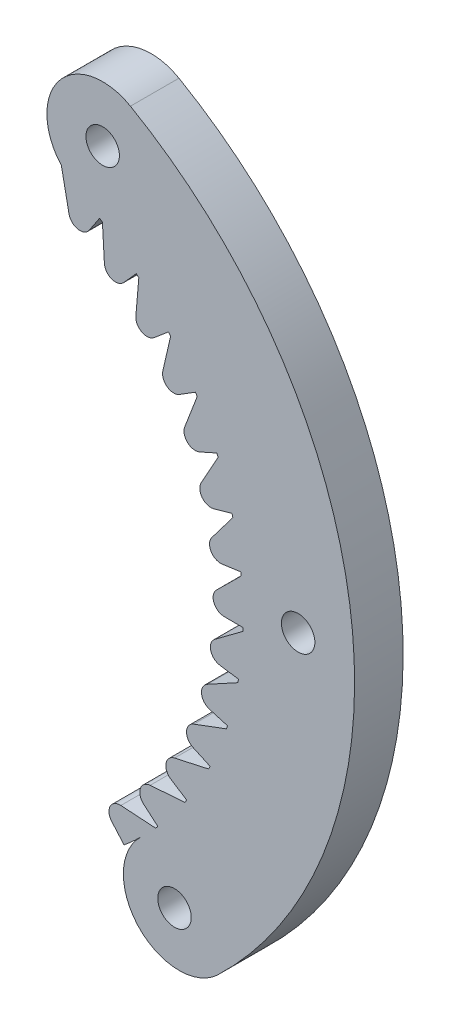
SolidWorks part; units mm, degrees
ref_plane "Plan de face" through (0, 0, 0) normal (0, 0, 1) x (1, 0, 0)
ref_plane "Plan de dessus" through (0, 0, 0) normal (0, 1, 0) x (1, 0, 0)
ref_plane "Plan de droite" through (0, 0, 0) normal (1, 0, 0) x (0, 0, -1)
sketch "Esquisse1" plane through (0, 0, 0) normal (0, 0, 1) x (1, 0, 0)
  line L0 (-13.1833, -31.6794) -> (-0.7137, -32.0392)
  arc A0 (-6.6972, -24.0098) -> (-13.1833, -31.6794) centre (12.6433, -46.9433) ccw
  arc A1 (-0.7137, -32.0392) -> (-6.1287, 33.617) centre (-26.0378, -1.0764) ccw
  arc A2 (-6.1287, 33.617) -> (-11.106, 24.9437) centre (-8.6173, 29.2803) ccw
  arc A3 (-6.6972, -24.0098) -> (-11.106, 24.9437) centre (-26.0378, -1.0764) ccw
extrude "Boss.-Extru.1" add sketch "Esquisse1" along normal blind 4.35
sketch "Esquisse2" plane through (0, 0, 0) normal (0, 0, -1) x (-1, 0, 0)
  line L0 (13.1833, -31.6794) -> (0.7137, -32.0392) construction
  line L1 (13.1833, -31.6794) -> (0.7137, -32.0392)
  arc A0 (0.7137, -32.0392) -> (6.6972, -24.0098) centre (0.5296, -25.6578) ccw
  arc A1 (13.1833, -31.6794) -> (6.6972, -24.0098) centre (-12.6433, -46.9433) ccw construction
  arc A2 (13.1833, -31.6794) -> (6.6972, -24.0098) centre (-12.6433, -46.9433) ccw
extrude "Enlèv. mat.-Extru.1" cut sketch "Esquisse2" against normal through all
fillet "Congé3" radius 5 2 edges at (-0.7137, -32.0392, 2.175) (-6.6972, -24.0098, 2.175)
sketch "Esquisse3" plane through (0, 0, 4.35) normal (0, 0, 1) x (1, 0, 0)
  circle A0 centre (-8.6173, 29.2803) radius 1.5
  circle A1 centre (8.9018, 0.2577) radius 1.5
  circle A2 centre (-2.1801, -26.6398) radius 1.5
extrude "Enlèv. mat.-Extru.2" cut sketch "Esquisse3" against normal through all
sketch "Esquisse4" plane through (0, 0, 4.35) normal (0, 0, 1) x (1, 0, 0)
  line L0 (-3.6669, -21.0649) -> (-4.9406, -19.9723) construction
  line L1 (-4.3658, -18.2162) -> (-1.2519, -17.9779) construction
  line L2 (-8.8914, 23.5408) -> (-9.8225, 22.1447) construction
  line L3 (-11.6351, 22.5036) -> (-12.247, 25.566) construction
  line L4 (-12.247, 25.566) -> (-12.3172, 25.9171) construction
  line L5 (-6.6972, -24.0098) -> (-7.8048, -22.7491) construction
  line L6 (-6.989, -21.0912) -> (-3.8725, -21.2928) construction
  line L7 (3.5531, -6.014) -> (1.8926, -5.7713) construction
  line L8 (1.4399, -3.9799) -> (3.9443, -2.1142) construction
  line L9 (2.5658, -10.1226) -> (0.9559, -9.649) construction
  line L10 (0.7593, -7.8118) -> (3.5011, -6.3165) construction
  line L11 (1.0111, -14.0518) -> (-0.5163, -13.3567) construction
  line L12 (-0.4528, -11.51) -> (2.4718, -10.4148) construction
  line L13 (-1.0803, -17.7235) -> (-2.4949, -16.8207) construction
  line L14 (-2.1726, -15.0013) -> (0.8769, -14.3278) construction
  line L15 (2.9726, 6.5654) -> (1.3588, 6.1053) construction
  line L16 (0.2107, 7.5531) -> (1.7288, 10.2822) construction
  line L17 (3.7586, 2.4136) -> (2.0961, 2.1848) construction
  line L18 (1.1628, 3.7795) -> (3.0493, 6.2683) construction
  line L19 (3.9533, -1.8075) -> (2.2752, -1.8005) construction
  line L20 (1.5753, -0.0904) -> (3.7927, 2.1086) construction
  line L21 (-2.7195, 17.7984) -> (-4.0022, 16.7165) construction
  line L22 (-5.6434, 17.5655) -> (-5.3791, 20.6773) construction
  line L23 (-0.2988, 14.3349) -> (-1.7209, 13.444) construction
  line L24 (-3.2265, 14.5152) -> (-2.5276, 17.5589) construction
  line L25 (1.6112, 10.5657) -> (0.078, 9.8833) construction
  line L26 (-1.2621, 11.1554) -> (-0.1425, 14.0708) construction
  line L27 (-5.6027, 20.8875) -> (-6.7208, 19.636) construction
  line L28 (-8.4649, 20.2461) -> (-8.6405, 23.3641) construction
  line L29 (-3.6669, -21.0649) -> (-4.9406, -19.9723)
  line L30 (-4.3658, -18.2162) -> (-1.2519, -17.9779)
  line L31 (-8.8914, 23.5408) -> (-9.8225, 22.1447)
  line L32 (-11.6351, 22.5036) -> (-12.247, 25.566)
  line L33 (-12.247, 25.566) -> (-12.3172, 25.9171)
  line L34 (-6.6972, -24.0098) -> (-7.8048, -22.7491)
  line L35 (-6.989, -21.0912) -> (-3.8725, -21.2928)
  line L36 (3.5531, -6.014) -> (1.8926, -5.7713)
  line L37 (1.4399, -3.9799) -> (3.9443, -2.1142)
  line L38 (2.5658, -10.1226) -> (0.9559, -9.649)
  line L39 (0.7593, -7.8118) -> (3.5011, -6.3165)
  line L40 (1.0111, -14.0518) -> (-0.5163, -13.3567)
  line L41 (-0.4528, -11.51) -> (2.4718, -10.4148)
  line L42 (-1.0803, -17.7235) -> (-2.4949, -16.8207)
  line L43 (-2.1726, -15.0013) -> (0.8769, -14.3278)
  line L44 (2.9726, 6.5654) -> (1.3588, 6.1053)
  line L45 (0.2107, 7.5531) -> (1.7288, 10.2822)
  line L46 (3.7586, 2.4136) -> (2.0961, 2.1848)
  line L47 (1.1628, 3.7795) -> (3.0493, 6.2683)
  line L48 (3.9533, -1.8075) -> (2.2752, -1.8005)
  line L49 (1.5753, -0.0904) -> (3.7927, 2.1086)
  line L50 (-2.7195, 17.7984) -> (-4.0022, 16.7165)
  line L51 (-5.6434, 17.5655) -> (-5.3791, 20.6773)
  line L52 (-0.2988, 14.3349) -> (-1.7209, 13.444)
  line L53 (-3.2265, 14.5152) -> (-2.5276, 17.5589)
  line L54 (1.6112, 10.5657) -> (0.078, 9.8833)
  line L55 (-1.2621, 11.1554) -> (-0.1425, 14.0708)
  line L56 (-5.6027, 20.8875) -> (-6.7208, 19.636)
  line L57 (-8.4649, 20.2461) -> (-8.6405, 23.3641)
  arc A0 (-4.3658, -18.2162) -> (-4.9406, -19.9723) centre (-4.2895, -19.2133) ccw construction
  arc A1 (-11.6351, 22.5036) -> (-9.8225, 22.1447) centre (-10.6545, 22.6995) ccw construction
  arc A2 (-12.3172, 25.9171) -> (-11.106, 24.9437) centre (-8.6173, 29.2803) ccw construction
  arc A3 (-6.6972, -24.0098) -> (-11.106, 24.9437) centre (-26.0378, -1.0764) ccw construction
  arc A4 (-6.989, -21.0912) -> (-7.8048, -22.7491) centre (-7.0535, -22.0891) ccw construction
  arc A5 (1.4399, -3.9799) -> (1.8926, -5.7713) centre (2.0373, -4.7818) ccw construction
  arc A6 (0.7593, -7.8118) -> (0.9559, -9.649) centre (1.2381, -8.6897) ccw construction
  arc A7 (-0.4528, -11.51) -> (-0.5163, -13.3567) centre (-0.1021, -12.4465) ccw construction
  arc A8 (-2.1726, -15.0013) -> (-2.4949, -16.8207) centre (-1.9569, -15.9777) ccw construction
  arc A9 (0.2107, 7.5531) -> (1.3588, 6.1053) centre (1.0846, 7.067) ccw construction
  arc A10 (1.1628, 3.7795) -> (2.0961, 2.1848) centre (1.9597, 3.1754) ccw construction
  arc A11 (1.5753, -0.0904) -> (2.2752, -1.8005) centre (2.2794, -0.8005) ccw construction
  arc A12 (-5.6434, 17.5655) -> (-4.0022, 16.7165) centre (-4.647, 17.4809) ccw construction
  arc A13 (-3.2265, 14.5152) -> (-1.7209, 13.444) centre (-2.2518, 14.2914) ccw construction
  arc A14 (-1.2621, 11.1554) -> (0.078, 9.8833) centre (-0.3286, 10.7969) ccw construction
  arc A15 (-8.4649, 20.2461) -> (-6.7208, 19.636) centre (-7.4665, 20.3023) ccw construction
  arc A16 (-4.3658, -18.2162) -> (-4.9406, -19.9723) centre (-4.2895, -19.2133) ccw
  arc A17 (-11.6351, 22.5036) -> (-9.8225, 22.1447) centre (-10.6545, 22.6995) ccw
  arc A18 (-12.3172, 25.9171) -> (-11.106, 24.9437) centre (-8.6173, 29.2803) ccw
  arc A19 (-6.6972, -24.0098) -> (-11.106, 24.9437) centre (-26.0378, -1.0764) ccw
  arc A20 (-6.989, -21.0912) -> (-7.8048, -22.7491) centre (-7.0535, -22.0891) ccw
  arc A21 (1.4399, -3.9799) -> (1.8926, -5.7713) centre (2.0373, -4.7818) ccw
  arc A22 (0.7593, -7.8118) -> (0.9559, -9.649) centre (1.2381, -8.6897) ccw
  arc A23 (-0.4528, -11.51) -> (-0.5163, -13.3567) centre (-0.1021, -12.4465) ccw
  arc A24 (-2.1726, -15.0013) -> (-2.4949, -16.8207) centre (-1.9569, -15.9777) ccw
  arc A25 (0.2107, 7.5531) -> (1.3588, 6.1053) centre (1.0846, 7.067) ccw
  arc A26 (1.1628, 3.7795) -> (2.0961, 2.1848) centre (1.9597, 3.1754) ccw
  arc A27 (1.5753, -0.0904) -> (2.2752, -1.8005) centre (2.2794, -0.8005) ccw
  arc A28 (-5.6434, 17.5655) -> (-4.0022, 16.7165) centre (-4.647, 17.4809) ccw
  arc A29 (-3.2265, 14.5152) -> (-1.7209, 13.444) centre (-2.2518, 14.2914) ccw
  arc A30 (-1.2621, 11.1554) -> (0.078, 9.8833) centre (-0.3286, 10.7969) ccw
  arc A31 (-8.4649, 20.2461) -> (-6.7208, 19.636) centre (-7.4665, 20.3023) ccw
  arc M7 (-6.1287, 33.617) -> (-11.106, 24.9437) centre (-8.6173, 29.2803) ccw
  arc M8 (-11.106, 24.9437) -> (-5.2295, -22.6869) centre (-26.0378, -1.0764) cw
extrude "Boss.-Extru.2" add sketch "Esquisse4" against normal through all contours L32 A17 L31 L33 M8 M7 | L57 A31 L56 M8 | L51 A28 L50 M8 | L53 A29 L52 M8 | L55 A30 L54 M8 | L45 A25 L44 M8 | L47 A26 L46 M8 | L49 A27 L48 M8 | L39 A22 L38 M8 | L37 A21 L36 M8 | L41 A23 L40 M8 | L43 A24 L42 M8 | L30 A16 L29 M8 | L35 A20 L34 A19 M8 region at (-10.7511, 23.4709, 4.35) region at (-7.439, 21.0448, 4.35) region at (-4.5154, 18.2122, 4.35) region at (-2.0188, 14.9969, 4.35) region at (0.0013, 11.4627, 4.35) region at (1.5048, 7.6798, 4.35) region at (2.4618, 3.7232, 4.35) region at (2.8535, -0.3287, 4.35) region at (2.6719, -4.3954, 4.35) region at (1.9208, -8.3963, 4.35) region at (0.615, -12.2519, 4.35) region at (-1.2196, -15.8858, 4.35) region at (-6.3197, -22.206, 4.35) region at (-3.5466, -19.2259, 4.35)
